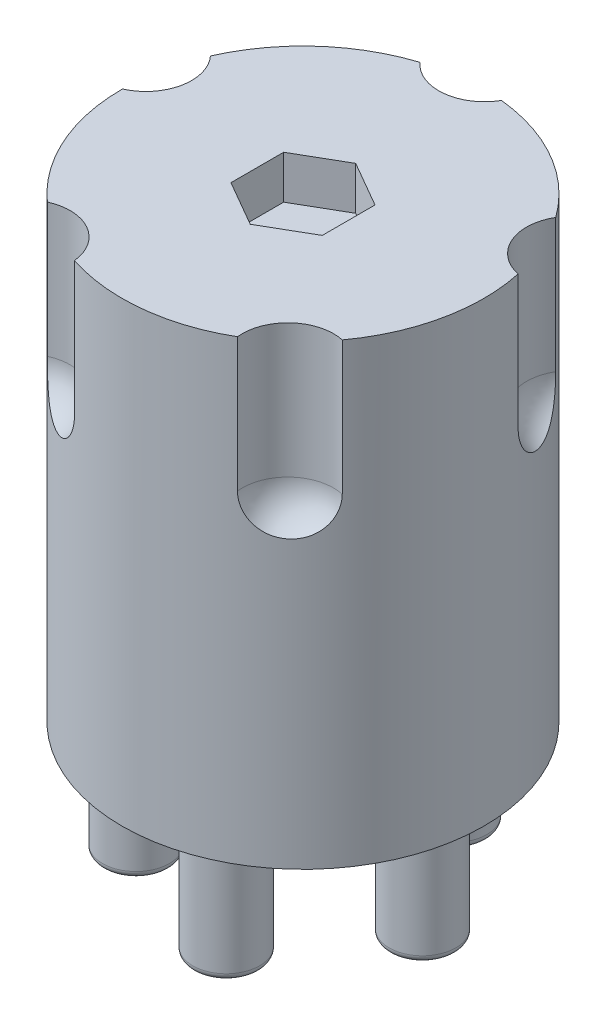
SolidWorks part; units mm, degrees
ref_plane "Front Plane" through (0, 0, 0) normal (0, 0, 1) x (1, 0, 0)
ref_plane "Top Plane" through (0, 0, 0) normal (0, 1, 0) x (1, 0, 0)
ref_plane "Right Plane" through (0, 0, 0) normal (1, 0, 0) x (0, 0, -1)
sketch "Sketch1" plane through (0, 0, 0) normal (0, 1, 0) x (1, 0, 0)
  circle A0 centre (0, 0) radius 25.75
  dimension "D1" = 51.5
extrude "Boss-Extrude1" add sketch "Sketch1" along normal blind 65
sketch "Sketch2" plane through (0, 0, 0) normal (0, -1, 0) x (1, 0, 0)
  circle A0 centre (0, 0) radius 17 construction
  circle A1 centre (17, 0) radius 4.75
  circle A2 centre (5.2533, -16.168) radius 4.75
  circle A3 centre (-13.7533, -9.9923) radius 4.75
  circle A4 centre (-13.7533, 9.9923) radius 4.75
  circle A5 centre (5.2533, 16.168) radius 4.75
  point P5 (7.9036, -19.623)
  point P6 (0, 0)
  point P7 (5.03, -15.4807)
  point P16 (0, 0)
  dimension "D2" = 9.5
  dimension "D3" = 34
  dimension "D1" = 5
extrude "Boss-Extrude2" add sketch "Sketch2" along normal blind 18
fillet "Fillet1" radius 1 5 edges at (5.2533, 0, 20.918) (-13.7533, 0, 14.7423) (-13.7533, 0, -5.2423) (5.2533, 0, -11.418) (17, 0, 4.75)
fillet "Fillet2" radius 1 5 edges at (-13.7533, -18, -14.7423) (-13.7533, -18, 5.2423) (5.2533, -18, 11.418) (17, -18, -4.75) (5.2533, -18, -20.918)
sketch "Sketch3" plane through (0, 65, 0) normal (0, 1, 0) x (1, 0, 0)
  line L1 (0, -7.5) -> (6.4952, -3.75)
  line L2 (6.4952, -3.75) -> (6.4952, 3.75)
  line L3 (6.4952, 3.75) -> (0, 7.5)
  line L4 (0, 7.5) -> (-6.4952, 3.75)
  line L5 (-6.4952, 3.75) -> (-6.4952, -3.75)
  line L6 (-6.4952, -3.75) -> (0, -7.5)
  circle A0 centre (0, 0) radius 6.4952 construction
  point P1 (6.6275, -3.5108)
  dimension "D1" = 15
extrude "Cut-Extrude1" cut sketch "Sketch3" against normal blind 6.15
sketch "Sketch4" plane through (0, 0, 0) normal (0, -1, 0) x (1, 0, 0)
  circle A0 centre (0, 0) radius 10
  dimension "D1" = 20
extrude "Cut-Extrude2" cut sketch "Sketch4" against normal blind 22
sketch "Sketch5" plane through (0, 22, 0) normal (0, -1, 0) x (1, 0, 0)
  circle A0 centre (0, 0) radius 4
  dimension "D1" = 8
extrude "Cut-Extrude3" cut sketch "Sketch5" against normal blind 11.5
chamfer "Chamfer2" distance 5 distance2 5 1 edges at (0, 22, -4)
sketch "Sketch6" plane through (0, 65, 0) normal (0, 1, 0) x (1, 0, 0)
  line L0 (-3.2476, -5.625) -> (-14.5, -25.1147) construction
  line L1 (-6.4952, -3.75) -> (0, -7.5) construction
  circle A0 centre (0, 0) radius 29 construction
  circle A1 centre (-14.5, -25.1147) radius 6.5
  circle A2 centre (-28.3663, 6.0294) radius 6.5
  circle A3 centre (-3.0313, 28.8411) radius 6.5
  circle A4 centre (26.4928, 11.7954) radius 6.5
  circle A5 centre (19.4048, -21.5512) radius 6.5
  point P3 (-27.741, 5.8965)
  point P5 (0, 0)
  point P16 (0, 0)
  point P19 (-18.9509, -32.8239)
  point P20 (-17.2809, -31.1436)
  dimension "D2" = 13
  dimension "D3" = 58
  dimension "D1" = 5
extrude "Cut-Extrude4" cut sketch "Sketch6" against normal blind 25
fillet "Fillet3" radius 6 5 edges at (-11.25, 40, 19.4856) (20.5548, 40, -9.1516) (-2.3519, 40, -22.3767) (-22.0083, 40, -4.678) (15.0554, 40, 16.7208)
